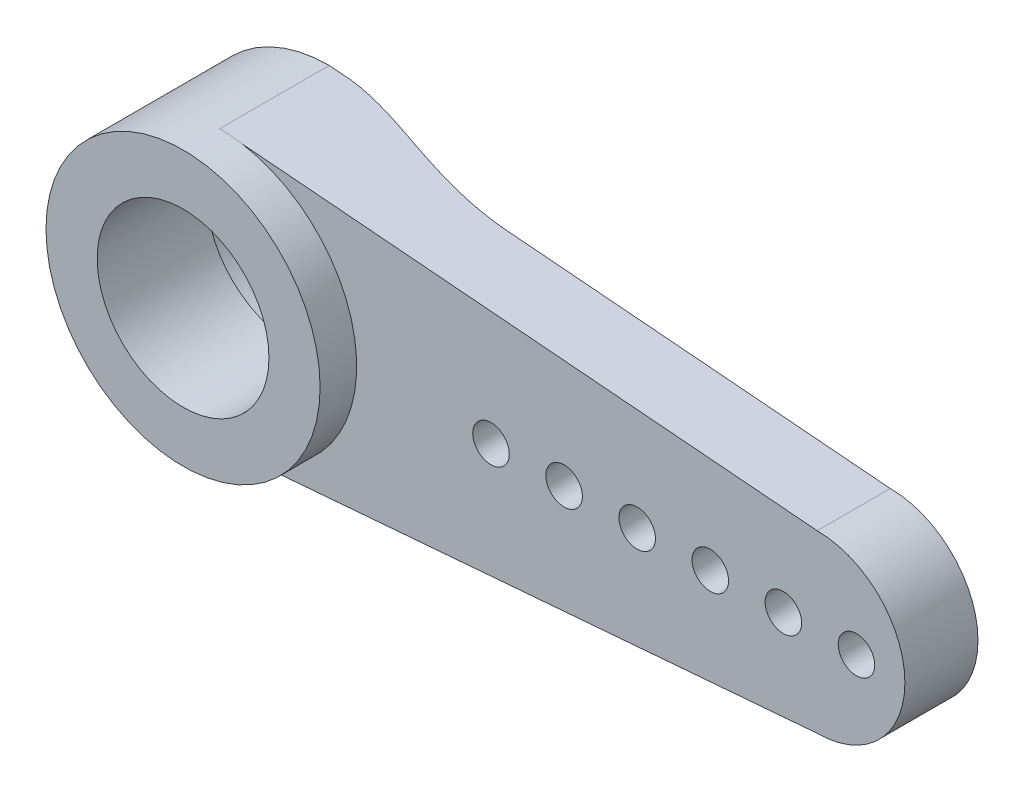
SolidWorks part; units mm, degrees
ref_plane "Front Plane" through (0, 0, 0) normal (0, 0, 1) x (1, 0, 0)
ref_plane "Top Plane" through (0, 0, 0) normal (0, 1, 0) x (1, 0, 0)
ref_plane "Right Plane" through (0, 0, 0) normal (1, 0, 0) x (0, 0, -1)
sketch "Sketch1" plane through (0, 0, 0) normal (0, 0, 1) x (1, 0, 0)
  line L0 (-6.5926, 3.75) -> (9.7574, 2.4)
  line L1 (-6.5926, -3.75) -> (9.7574, -2.4)
  arc A0 (-5.9775, 3.6992) -> (-5.9775, -3.6992) centre (-6.5926, 0) ccw
  arc A1 (9.7574, -2.4) -> (9.7574, 2.4) centre (9.7574, 0) ccw
  circle A2 centre (-6.5926, 0) radius 2.35
  dimension "D1" = 7.5
  dimension "D2" = 4.8
  dimension "D4" = 4.7
  dimension "D3" = 16.35
extrude "Boss-Extrude1" add sketch "Sketch1" along normal blind 2 contours L1 A1 L0 A0 A2 region at (1.1375, 0, 0)
sketch "Sketch2" plane through (0, 0, 2) normal (0, 0, 1) x (1, 0, 0)
  line L2 (-6.5926, -3.75) -> (9.7574, -2.4)
  line L3 (9.7574, 2.4) -> (-6.5926, 3.75)
  circle A0 centre (-6.5926, 0) radius 2.35 construction
  circle A1 centre (-6.5926, 0) radius 2.35
  arc A2 (9.7574, -2.4) -> (9.7574, 2.4) centre (9.7574, 0) ccw
  arc A3 (-6.5926, 3.75) -> (-6.5926, -3.75) centre (-6.5926, 0) ccw
  arc A5 (-6.5926, 3.75) -> (-6.5926, -3.75) centre (-6.5926, 0) ccw
  arc A6 (-6.5926, 3.75) -> (-6.5926, -3.75) centre (-6.5926, 0) cw
  dimension "D1" = 0
extrude "Boss-Extrude2" add sketch "Sketch2" along normal blind 1
sketch "Sketch3" plane through (0, 0, 0) normal (0, 0, -1) x (-1, 0, 0)
  line L2 (-9.7574, -2.4) -> (6.5926, -3.75)
  line L3 (6.5926, 3.75) -> (-9.7574, 2.4)
  circle A0 centre (6.5926, 0) radius 2.35 construction
  circle A1 centre (6.5926, 0) radius 2.35
  arc A2 (6.5926, -3.75) -> (6.5926, 3.75) centre (6.5926, 0) ccw
  arc A3 (-9.7574, 2.4) -> (-9.7574, -2.4) centre (-9.7574, 0) ccw
  arc A4 (6.5926, -3.75) -> (6.5926, 3.75) centre (6.5926, 0) ccw
  circle A6 centre (6.5926, 0) radius 2.75
  arc A7 (6.5926, 3.75) -> (6.5926, -3.75) centre (6.5926, 0) ccw
  line M6 (-9.7574, -2.4) -> (6.5926, -3.75)
  arc M7 (6.5926, -3.75) -> (6.5926, 3.75) centre (6.5926, 0) ccw
  line M8 (6.5926, 3.75) -> (-9.7574, 2.4)
  dimension "D2" = 5.5
  dimension "D1" = 0
extrude "Boss-Extrude3" add sketch "Sketch3" along normal blind 1 contours A7 A6 M8 M6 M7 region at (-2.9486, 0, 0)
fillet "Fillet1" radius 5 1 edges at (-2.8426, 0, 0)
sketch "Sketch4" plane through (0, 0, 0) normal (0, 0, -1) x (-1, 0, 0)
  circle A0 centre (-10.8328, 0) radius 0.5
  circle A1 centre (-8.8328, 0) radius 0.5
  circle A2 centre (-6.8328, 0) radius 0.5
  circle A3 centre (-4.8328, 0) radius 0.5
  circle A4 centre (-2.8328, 0) radius 0.5
  circle A5 centre (-0.8328, 0) radius 0.5
  dimension "D1" = 1
  dimension "D2" = 6
extrude "Cut-Extrude1" cut sketch "Sketch4" against normal up to next
